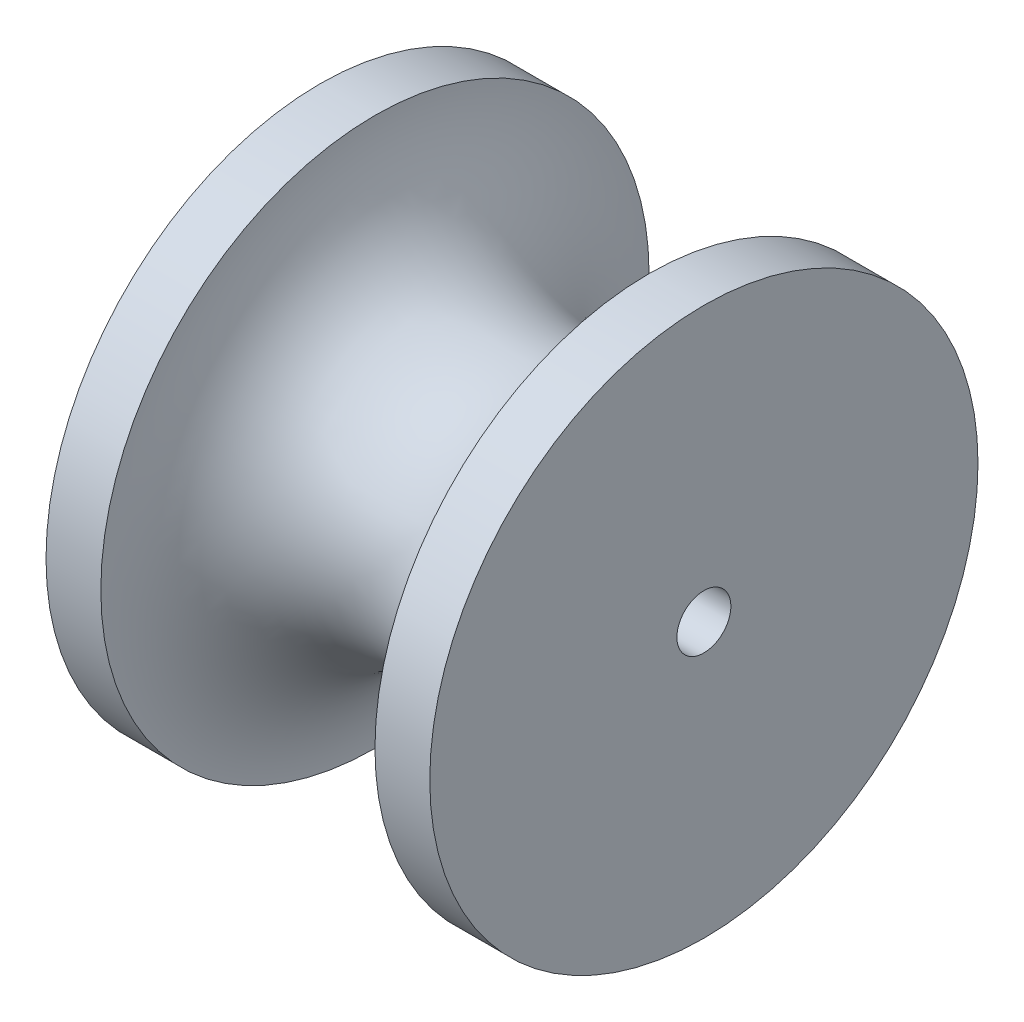
SolidWorks part; units mm, degrees
ref_plane "Front Plane" through (0, 0, 0) normal (0, 0, 1) x (1, 0, 0)
ref_plane "Top Plane" through (0, 0, 0) normal (0, 1, 0) x (1, 0, 0)
ref_plane "Right Plane" through (0, 0, 0) normal (1, 0, 0) x (0, 0, -1)
sketch "Sketch1" plane through (0, 0, 0) normal (0, 0, 1) x (1, 0, 0)
  line L0 (-35.56, 0) -> (-30.48, 0)
  line L1 (-5.08, 0) -> (0, 0)
  line L2 (-35.56, 0) -> (-35.56, -25.4)
  line L3 (-35.56, -25.4) -> (0, -25.4)
  line L4 (0, -25.4) -> (0, 0)
  arc A0 (-30.48, 0) -> (-5.08, 0) centre (-17.78, 0) ccw
  point P7 (0, 0)
  dimension "D1" = 35.56
  dimension "D3" = 12.7
  dimension "D2" = 25.4
  dimension "D4" = 5.08
revolve "Revolve1" add sketch "Sketch1" angle 360 about L3
sketch "Sketch5" plane through (-35.56, 0, 0) normal (-1, 0, 0) x (0, 0, 1)
  circle A0 centre (0, -25.4) radius 2.5
  circle A2 centre (0, -25.4) radius 25.4 construction
  dimension "D1" = 5
extrude "Cut-Extrude2" cut sketch "Sketch5" against normal blind 35.56
